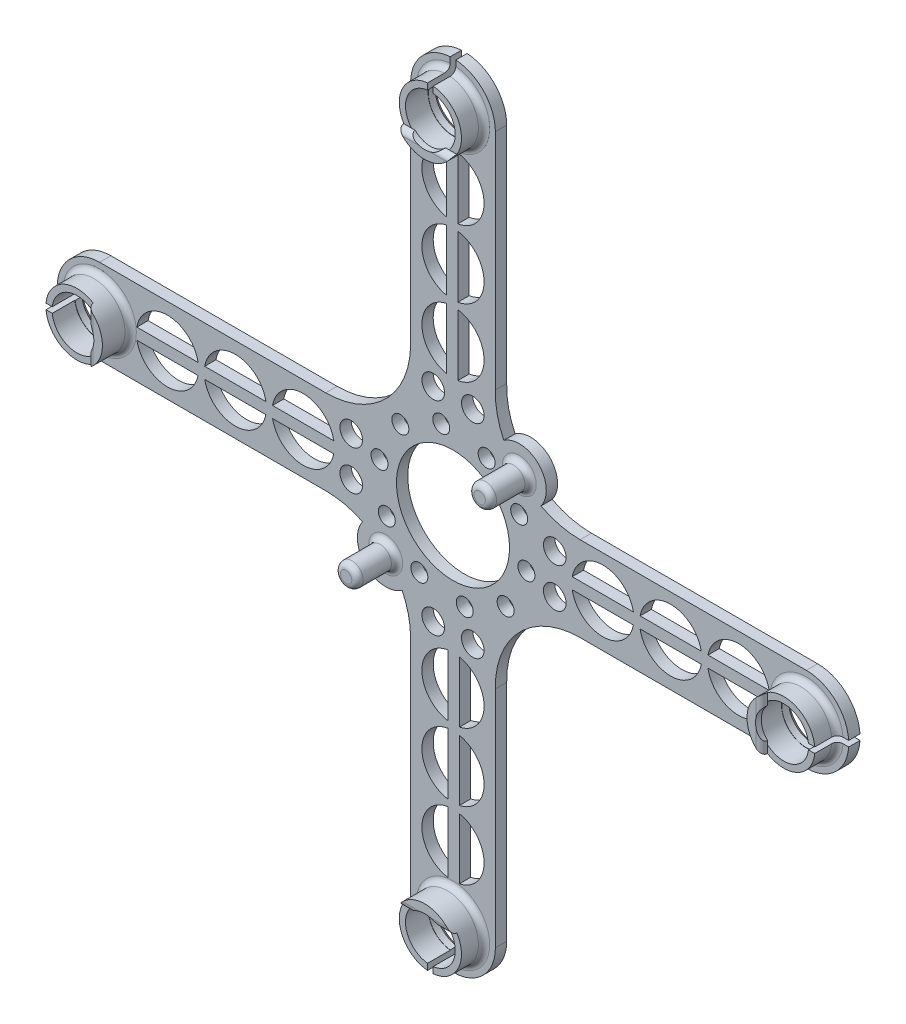
SolidWorks part; units mm, degrees
material "ABS"
ref_plane "Front Plane" through (0, 0, 0) normal (0, 0, 1) x (1, 0, 0)
ref_plane "Top Plane" through (0, 0, 0) normal (0, 1, 0) x (1, 0, 0)
ref_plane "Right Plane" through (0, 0, 0) normal (1, 0, 0) x (0, 0, -1)
sketch "Frame" plane through (0, 0, 0) normal (0, 0, 1) x (1, 0, 0)
  line L4 (-7.5, 62.5) -> (-7.5, 22.017)
  line L5 (7.5, 62.5) -> (7.5, 22.9557)
  line L6 (62.5, 7.5) -> (22.4931, 7.5)
  line L7 (-62.5, -7.5) -> (-22.5, -7.5)
  line L8 (-22.5, 7.5) -> (-62.5, 7.5)
  line L9 (22.496, -7.5) -> (62.5, -7.5)
  line L10 (-7.5, -22.5) -> (-7.5, -62.5)
  line L11 (7.5, -22.8466) -> (7.5, -62.5)
  line L26 (0, 0) -> (161.945, 0) construction
  line L27 (0, 0) -> (-187.6851, 0) construction
  line L28 (0, 0) -> (0, 122.1151) construction
  line L29 (0, 0) -> (0, -123.7083) construction
  circle A0 centre (0, -62.5) radius 4.35
  circle A1 centre (-62.5, 0) radius 4.35
  circle A2 centre (0, 62.5) radius 4.35
  circle A3 centre (62.5, 0) radius 4.35
  arc A4 (62.5, -7.5) -> (62.5, 7.5) centre (62.5, 0) ccw
  arc A5 (-7.5, -62.5) -> (7.5, -62.5) centre (0, -62.5) ccw
  arc A6 (-62.5, 7.5) -> (-62.5, -7.5) centre (-62.5, 0) ccw
  arc A7 (7.5, 62.5) -> (-7.5, 62.5) centre (0, 62.5) ccw
  arc A8 (7.5, 22.9557) -> (22.4931, 7.5) centre (22.4931, 22.5) ccw
  arc A9 (-7.5, 22.017) -> (-22.5, 7.5) centre (-22.4922, 22.5) cw
  arc A10 (-22.5, -7.5) -> (-7.5, -22.5) centre (-22.5, -22.5) cw
  arc A11 (7.5, -22.8466) -> (22.496, -7.5) centre (22.496, -22.5) cw
  arc A12 (-15.9829, -8.9897) -> (-8.9897, -15.9829) centre (-11.8934, -11.8934) ccw
  arc A13 (15.5546, 9.2012) -> (8.9896, 15.9687) centre (11.7266, 12.0557) ccw
  point P0 (0, 0)
  point P5 (64.6214, -5.3787)
  point P6 (57.5344, -45.6231)
  point P34 (7.5001, -7.5)
  point P43 (48.6535, -45.6231)
  point P44 (64.6213, 5.3787)
  point P45 (0, 0)
  point P79 (0, 0)
  point P82 (0, 0)
  point P85 (0, 0)
  dimension "D3" = 4
  dimension "D6" = 15
  dimension "D7" = 4
  dimension "D10" = 8.7
  dimension "D14" = 7.5
  dimension "D20" = 15
  dimension "D21" = 15
  dimension "D22" = 15
  dimension "D18" = 7.5
  dimension "D23" = 62.5
  dimension "D29" = 7.5
extrude "Main Frame Extrude" add sketch "Frame" along normal blind 2 contours L11 A11 L9 L6 A8 L4 A9 L8 L7 A10 L10 A3 | A10 A12 | A8 A13 region at (-0.0001, -0.0006, 0) region at (13.275, 13.5578, 0) region at (-13.5002, -13.5002, 0)
ref_plane "Top of Frame" through (0, 0, 2) normal (0, 0, 1) x (1, 0, 0)
sketch "Sketch2" plane through (0, 0, 2) normal (0, 0, 1) x (1, 0, 0)
  circle A0 centre (-11.8934, -11.8934) radius 2
  circle A1 centre (11.7266, 12.0557) radius 2
  dimension "D1" = 4
  dimension "D2" = 4
extrude "Posts" add sketch "Sketch2" along normal blind 7
fillet "Fillet1" radius 1 1 edges at (-9.8934, -11.8934, 2)
fillet "Fillet2" radius 1 1 edges at (13.7266, 12.0557, 2)
fillet "Fillet3" radius 1 1 edges at (-9.8934, -11.8934, 9)
fillet "Fillet4" radius 1 1 edges at (13.7266, 12.0557, 9)
sketch "Frame Cut Outs" plane through (0, 0, 2) normal (0, 0, 1) x (1, 0, 0)
  line L0 (-0.0001, -50.5) -> (-0.0001, -38.5) construction
  line L1 (31.9088, -0.8624) -> (21.0921, -0.8624)
  line L2 (31.9088, 1.1376) -> (21.0921, 1.1376)
  line L3 (50.5004, 0.102) -> (38.5004, 0.1198) construction
  line L4 (-0.0001, 50.5) -> (-0.0001, 38.5) construction
  line L5 (-50.5, -0.0955) -> (-38.5, -0.0955) construction
  line L6 (-0.8624, -31.932) -> (-0.8624, -21.068)
  line L7 (1.1376, -31.8811) -> (1.1376, -21.1189)
  line L8 (-31.9159, 0.8624) -> (-21.0841, 0.8624)
  line L9 (-31.9004, -1.1376) -> (-21.0996, -1.1376)
  line L10 (0.8624, 31.9319) -> (0.8624, 21.0681)
  line L11 (-1.1376, 31.8811) -> (-1.1376, 21.1189)
  line L12 (-0.8624, -33.068) -> (-0.8624, -43.932)
  line L13 (1.1376, -33.1189) -> (1.1376, -43.8811)
  line L14 (-1.1376, 33.1189) -> (-1.1376, 43.8811)
  line L15 (0.8624, 33.0681) -> (0.8624, 43.9319)
  line L16 (-1.1376, 45.1189) -> (-1.1376, 55.8811)
  line L17 (0.8624, 45.0681) -> (0.8624, 55.9319)
  line L18 (1.1376, -45.119) -> (1.1376, -55.881)
  line L19 (-0.8624, -45.068) -> (-0.8624, -55.932)
  line L20 (33.0889, -0.8624) -> (43.912, -0.8624)
  line L21 (33.0954, 1.1376) -> (43.9055, 1.1376)
  line L22 (45.0857, -0.8624) -> (55.9152, -0.8624)
  line L23 (45.0988, 1.1376) -> (55.9021, 1.1376)
  line L24 (-33.0841, 0.8624) -> (-43.9159, 0.8624)
  line L25 (-33.0996, -1.1376) -> (-43.9004, -1.1376)
  line L26 (-45.0996, -1.1376) -> (-55.9004, -1.1376)
  line L27 (-45.0841, 0.8624) -> (-55.9159, 0.8624)
  arc A0 (-55.9004, -1.1376) -> (-45.0996, -1.1376) centre (-50.5, -0.0955) ccw
  arc A2 (-43.9004, -1.1376) -> (-33.0996, -1.1376) centre (-38.5, -0.0955) ccw
  arc A3 (-21.0841, 0.8624) -> (-31.9159, 0.8624) centre (-26.5, -0.0955) ccw
  arc A4 (-0.8624, -21.068) -> (-0.8624, -31.932) centre (0, -26.5) ccw
  arc A5 (-1.1376, 55.8811) -> (-1.1376, 45.1189) centre (-0.0001, 50.5) ccw
  arc A7 (55.9021, 1.1376) -> (45.0988, 1.1376) centre (50.5004, 0.102) ccw
  arc A8 (-0.8624, -45.068) -> (-0.8624, -55.932) centre (-0.0001, -50.5) ccw
  circle A9 centre (62.5, 0) radius 4.35 construction
  arc A11 (1.1376, -43.8811) -> (1.1376, -33.1189) centre (-0.0001, -38.5) ccw
  arc A12 (1.1376, -31.8811) -> (1.1376, -21.1189) centre (0, -26.5) ccw
  arc A13 (-31.9004, -1.1376) -> (-21.0996, -1.1376) centre (-26.5, -0.0955) ccw
  arc A14 (43.9055, 1.1376) -> (33.0954, 1.1376) centre (38.5004, 0.1198) ccw
  arc A15 (21.0921, -0.8624) -> (31.9088, -0.8624) centre (26.5005, 0.1376) ccw
  arc A16 (31.9088, 1.1376) -> (21.0921, 1.1376) centre (26.5005, 0.1376) ccw
  arc A17 (-1.1376, 43.8811) -> (-1.1376, 33.1189) centre (-0.0001, 38.5) ccw
  arc A18 (0.8624, 21.0681) -> (0.8624, 31.9319) centre (-0.0001, 26.5) ccw
  arc A19 (-1.1376, 31.8811) -> (-1.1376, 21.1189) centre (-0.0001, 26.5) ccw
  circle A20 centre (0, 0) radius 10
  circle A21 centre (-11.7065, -5.9878) radius 1.5
  circle A22 centre (-12.9903, 2.0367) radius 1.5
  circle A23 centre (-9.3122, 9.2832) radius 1.5
  circle A24 centre (-2.0772, 12.9839) radius 1.5
  circle A25 centre (5.9513, 11.7251) radius 1.5
  circle A26 centre (11.7065, 5.9878) radius 1.5
  circle A27 centre (12.9903, -2.0367) radius 1.5
  circle A28 centre (9.3122, -9.2832) radius 1.5
  circle A29 centre (2.0772, -12.9839) radius 1.5
  circle A30 centre (-5.9513, -11.7251) radius 1.5
  arc A31 (0.8624, 45.0681) -> (0.8624, 55.9319) centre (-0.0001, 50.5) ccw
  arc A32 (0.8624, 33.0681) -> (0.8624, 43.9319) centre (-0.0001, 38.5) ccw
  arc A33 (1.1376, -55.881) -> (1.1376, -45.119) centre (-0.0001, -50.5) ccw
  arc A34 (-0.8624, -33.068) -> (-0.8624, -43.932) centre (-0.0001, -38.5) ccw
  arc A35 (45.0857, -0.8624) -> (55.9152, -0.8624) centre (50.5004, 0.102) ccw
  arc A36 (33.0889, -0.8624) -> (43.912, -0.8624) centre (38.5004, 0.1198) ccw
  arc A37 (-45.0841, 0.8624) -> (-55.9159, 0.8624) centre (-50.5, -0.0955) ccw
  arc A38 (-33.0841, 0.8624) -> (-43.9159, 0.8624) centre (-38.5, -0.0955) ccw
  circle A39 centre (-18, -3.5) radius 2
  circle A40 centre (-18, 3.5) radius 2
  circle A41 centre (3.5, 18) radius 2
  circle A42 centre (-3.5, 18) radius 2
  circle A43 centre (18, -3.5) radius 2
  circle A44 centre (18, 3.5) radius 2
  circle A45 centre (-3.5, -18) radius 2
  circle A46 centre (3.5, -18) radius 2
  point P62 (0, 0)
  point P79 (0, 0)
  point P120 (0, 0)
  dimension "D4" = 12
  dimension "D15" = 1
  dimension "D14" = 1
  dimension "D17" = 10
  dimension "D18" = 4
  dimension "D19" = 4
  dimension "D7" = 12
  dimension "D9" = 12
  dimension "D11" = 12
  dimension "D13" = 12
  dimension "D20" = 18
  dimension "D21" = 0
  dimension "D22" = 3.5
  dimension "D23" = 3.5
  dimension "D6" = 3
  dimension "D8" = 3
  dimension "D10" = 3
  dimension "D12" = 3
  dimension "D16" = 4
  dimension "D24" = 4
extrude "Top of Frame Cutouts" cut sketch "Frame Cut Outs" against normal through all
sketch "Sketch5" plane through (0, 0, 2) normal (0, 0, 1) x (1, 0, 0)
  circle A0 centre (62.5, 0) radius 5.5
  circle A1 centre (62.5, 0) radius 4.4
  circle A2 centre (0, -62.5) radius 5.5
  circle A3 centre (0, -62.5) radius 4.4
  circle A4 centre (-62.5, 0) radius 5.5
  circle A5 centre (-62.5, 0) radius 4.4
  circle A6 centre (0, 62.5) radius 5.5
  circle A7 centre (0, 62.5) radius 4.4
  point P16 (0, 0)
  dimension "D1" = 4
  dimension "D2" = 8.8
  dimension "D3" = 11
extrude "Boss-Extrude4" add sketch "Sketch5" along normal blind 4
ref_plane "Top of Motor Mount" through (0, 0, 6) normal (0, 0, 1) x (1, 0, 0)
chamfer "Motor Mount Chamfer" distance 0.8 angle 45 4 edges at (66.85, 0, 0) (4.35, -62.5, 0) (-58.15, 0, 0) (4.35, 62.5, 0)
fillet "Motor Mount Fillet Bottom" radius 1 4 edges at (5.5, -62.5, 2) (-57, 0, 2) (5.5, 62.5, 2) (68, 0, 2)
sketch "Sketch13" plane through (0, 0, 6) normal (0, 0, 1) x (1, 0, 0)
  line L0 (0, 0) -> (0, 136.9008) construction
  line L1 (0.5, 66.5) -> (-0.5, 66.5)
  line L2 (0.5, 66.5) -> (0.5, 71.5)
  line L3 (0.5, 71.5) -> (-0.5, 71.5)
  line L4 (-0.5, 66.5) -> (-0.5, 71.5)
  line L5 (0, 0) -> (-128.4429, 0) construction
  line L6 (0, 0) -> (151.4525, 0) construction
  line L7 (0, 0) -> (0, -106.3754) construction
  line L8 (66.5, -0.5) -> (66.5, 0.5)
  line L9 (66.5, -0.5) -> (71.5, -0.5)
  line L10 (71.5, -0.5) -> (71.5, 0.5)
  line L11 (66.5, 0.5) -> (71.5, 0.5)
  line L12 (0, 0) -> (136.9008, 0) construction
  line L13 (-0.5, -66.5) -> (0.5, -66.5)
  line L14 (-0.5, -66.5) -> (-0.5, -71.5)
  line L15 (-0.5, -71.5) -> (0.5, -71.5)
  line L16 (0.5, -66.5) -> (0.5, -71.5)
  line L17 (0, 0) -> (0, -136.9008) construction
  line L18 (-66.5, 0.5) -> (-66.5, -0.5)
  line L19 (-66.5, 0.5) -> (-71.5, 0.5)
  line L20 (-71.5, 0.5) -> (-71.5, -0.5)
  line L21 (-66.5, -0.5) -> (-71.5, -0.5)
  line L22 (0, 0) -> (-136.9008, 0) construction
  circle A1 centre (0, 62.5) radius 4.4 construction
  point P6 (0, 66.5)
  point P22 (66.5, 0)
  point P28 (0, -66.5)
  point P34 (-66.5, 0)
  point P35 (0, 0)
  dimension "D1" = 1
  dimension "D2" = 5
  dimension "D3" = 0
  dimension "D4" = 4
  dimension "D5" = 4
extrude "Cut-Extrude1" cut sketch "Sketch13" against normal blind 10
sketch "Sketch14" plane through (0, 0, 6) normal (0, 0, 1) x (1, 0, 0)
  line L0 (-4.6906, -59.628) -> (-2.6906, -59.628)
  line L1 (4.6906, -59.628) -> (2.6906, -59.628)
  line L2 (-59.628, 4.6906) -> (-59.628, 2.6906)
  line L3 (-59.628, -4.6906) -> (-59.628, -2.6906)
  line L4 (4.6906, 59.628) -> (2.6906, 59.628)
  line L5 (-4.6906, 59.628) -> (-2.6906, 59.628)
  line L6 (59.628, -4.6906) -> (59.628, -2.6906)
  line L7 (59.628, 4.6906) -> (59.628, 2.6906)
  arc A1 (0.5, -67.9772) -> (-0.5, -67.9772) centre (0, -62.5) ccw construction
  arc A2 (-4.6906, -59.628) -> (4.6906, -59.628) centre (0, -62.5) cw
  arc A3 (-2.6906, -59.628) -> (2.6906, -59.628) centre (0, -62.3186) cw
  arc A4 (-59.628, 4.6906) -> (-59.628, -4.6906) centre (-62.5, 0) cw
  arc A5 (-59.628, 2.6906) -> (-59.628, -2.6906) centre (-62.3186, 0) cw
  arc A6 (4.6906, 59.628) -> (-4.6906, 59.628) centre (0, 62.5) cw
  arc A7 (2.6906, 59.628) -> (-2.6906, 59.628) centre (0, 62.3186) cw
  arc A8 (59.628, -4.6906) -> (59.628, 4.6906) centre (62.5, 0) cw
  arc A9 (59.628, -2.6906) -> (59.628, 2.6906) centre (62.3186, 0) cw
  point P30 (0, 0)
  dimension "D1" = 2
  dimension "D2" = 2
  dimension "D3" = 4
extrude "Motor Mount Top" add sketch "Sketch14" along normal blind 1
fillet "Fillet23" radius 1 8 edges at (-3.6906, -59.628, 7) (3.6906, -59.628, 7) (59.628, -3.6906, 7) (59.628, 3.6906, 7) (-3.6906, 59.628, 7) (3.6906, 59.628, 7) (-59.628, 3.6906, 7) (-59.628, -3.6906, 7)
